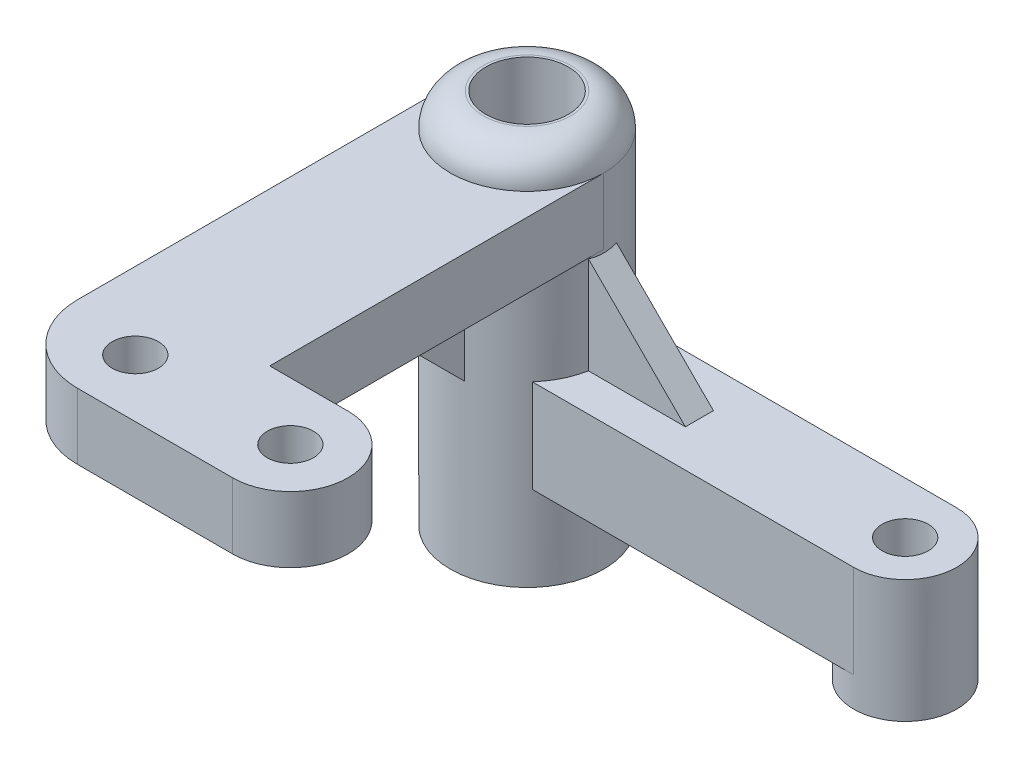
SolidWorks part; units mm, degrees
ref_plane "Front Plane" through (0, 0, 0) normal (0, 0, 1) x (1, 0, 0)
ref_plane "Top Plane" through (0, 0, 0) normal (0, 1, 0) x (1, 0, 0)
ref_plane "Right Plane" through (0, 0, 0) normal (1, 0, 0) x (0, 0, -1)
sketch "Sketch2" plane through (0, 0, 0) normal (0, 1, 0) x (1, 0, 0)
  line L0 (0, 0) -> (0, 22.6) construction
  line L1 (-4.65, 0) -> (-4.65, 22.6)
  line L2 (4.65, 0) -> (4.65, 22.6)
  line L3 (0, -1.15) -> (-9.4, -1.15) construction
  line L4 (0, -4.65) -> (-9.4, -4.65)
  line L5 (0, 2.35) -> (-9.4, 2.35)
  arc A0 (-4.65, 0) -> (4.65, 0) centre (0, 0) ccw
  arc A1 (4.65, 22.6) -> (-4.65, 22.6) centre (0, 22.6) ccw
  arc A2 (0, -4.65) -> (0, 2.35) centre (0, -1.15) ccw
  arc A3 (-9.4, 2.35) -> (-9.4, -4.65) centre (-9.4, -1.15) ccw
  circle A4 centre (-9.4, -1.15) radius 1.4
  circle A5 centre (0, -1.15) radius 1.4
  circle A6 centre (0, 22.6) radius 2.5
  point P3 (0, 11.3)
  point P8 (0, 27.25)
  point P9 (0, -4.65)
  point P12 (-4.7, -1.15)
  point P17 (-12.9, -1.15)
  dimension "D5" = 2.8
  dimension "D6" = 5
  dimension "D1" = 9.3
  dimension "D2" = 31.9
  dimension "D3" = 9.4
  dimension "D4" = 7
extrude "Boss-Extrude1" add sketch "Sketch2" along normal blind 4 contours L5 A3 L4 A0 L1 A4 | A0 A2 L5 L1 A5 | A2 A0 L2 A1 L1 L5 region at (-7.8846, 0, 1.3741) region at (-4.5426, 0, -1.175) region at (0.1436, 0, -12.974)
sketch "Sketch3" plane through (0, 0, 0) normal (0, -1, 0) x (1, 0, 0)
  circle A0 centre (0, -22.6) radius 4.65
  circle A1 centre (0, -22.6) radius 2.5 construction
  circle A2 centre (0, -22.6) radius 2.5
extrude "Boss-Extrude2" add sketch "Sketch3" along normal offset from surface (16.8 mm away) 20.8 up to face at (-3.0481, 4, -6.3267)
sketch "Sketch5" plane through (0, 4, 0) normal (0, 1, 0) x (1, 0, 0)
  circle A1 centre (0, 22.6) radius 2.5
  circle A2 centre (0, 22.6) radius 2.5
  circle A3 centre (0, 22.6) radius 4.65
  circle A4 centre (0, 22.6) radius 4.65
  dimension "D1" = 0
  dimension "D2" = 0
extrude "Boss-Extrude3" add sketch "Sketch5" along normal offset from surface (2 mm away) 22.8 up to face at (0, -16.8, -20.1)
fillet "Fillet1" radius 2 1 edges at (0, 6, -17.95)
sketch "Sketch6" plane through (0, 0, 0) normal (1, 0, 0) x (0, 0, -1)
  line L0 (11.45, 0) -> (17.95, -6.5)
  line L1 (17.95, 0) -> (17.95, -16.8) construction
  line L2 (2.35, 0) -> (22.6, 0) construction
  dimension "D1" = 6.5
  dimension "D2" = 45
rib "Rib1" sketch "Sketch6" sketch "Sketch6" thickness 1.6 extrusion direction parallel to sketch draft on no parameters "D1"=1.6
mirror "Mirror1" about plane through (0, 0, 0) normal (1, 0, 0) of bodies 103
delete or keep bodies "Body-Delete/Keep 1" type keep bodies bodies 104
ref_plane "Plane1" through (0, -6, 0) normal (0, 1, 0) x (1, 0, 0)
sketch "Sketch7" plane through (0, -6, 0) normal (0, 1, 0) x (1, 0, 0)
  line L0 (0, 22.6) -> (22.925, 22.6) construction
  line L1 (0, 25.725) -> (22.925, 25.725)
  line L2 (0, 19.475) -> (22.925, 19.475)
  arc A0 (0, 25.725) -> (0, 19.475) centre (0, 22.6) ccw
  arc A1 (22.925, 19.475) -> (22.925, 25.725) centre (22.925, 22.6) ccw
  circle A2 centre (0, 22.6) radius 4.65 construction
  arc A3 (3.4434, 19.475) -> (3.4434, 25.725) centre (0, 22.6) ccw
  point P3 (11.4625, 22.6)
  point P8 (26.05, 22.6)
  point P9 (-4.65, 22.6)
  dimension "D1" = 6.25
  dimension "D2" = 30.7
extrude "Boss-Extrude4" add sketch "Sketch7" against normal blind 5.65 contours A3 L2 A1 L1 region at (14.8339, -6, -22.6)
sketch "Sketch8" plane through (0, -11.65, 0) normal (0, -1, 0) x (1, 0, 0)
  circle A0 centre (22.925, -22.6) radius 3.125
extrude "Boss-Extrude5" add sketch "Sketch8" along normal blind 1.8
sketch "Sketch9" plane through (0, -13.45, 0) normal (0, -1, 0) x (1, 0, 0)
  circle A0 centre (22.925, -22.6) radius 1.4
extrude "Cut-Extrude1" cut sketch "Sketch9" against normal through all
ref_plane "Plane2" through (0, 0, -22.6) normal (0, 0, 1) x (1, 0, 0)
sketch "Sketch10" plane through (0, 0, -22.6) normal (0, 0, 1) x (1, 0, 0)
  line L0 (4.65, -0.2) -> (10.45, -6)
  line L1 (4.65, -16.8) -> (4.65, -11.65) construction
  line L4 (3.4434, -6) -> (22.925, -6) construction
  line L5 (4.65, -6) -> (4.65, 0) construction
  dimension "D1" = 45
  dimension "D2" = 5.8
rib "Rib2" sketch "Sketch10" sketch "Sketch10" thickness 1.7 extrusion direction parallel to sketch draft on no parameters "D1"=1.7
